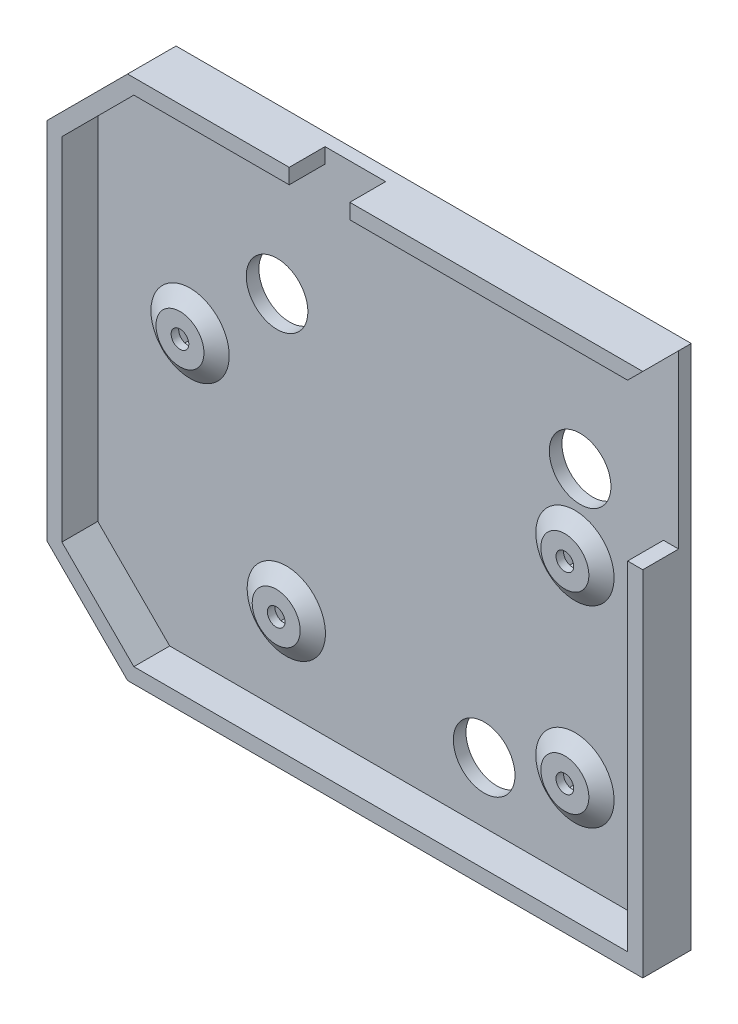
SolidWorks part; units mm, degrees
material "Delrin 2700 NC010, copolymère d'acétal à faible viscosité (SS)"
ref_plane "Plan de face" through (0, 0, 0) normal (0, 0, 1) x (1, 0, 0)
ref_plane "Plan de dessus" through (0, 0, 0) normal (0, 1, 0) x (1, 0, 0)
ref_plane "Plan de droite" through (0, 0, 0) normal (1, 0, 0) x (0, 0, -1)
sketch "Esquisse1" plane through (0, 0, 0) normal (0, 0, 1) x (1, 0, 0)
  line L0 (0, -85) -> (16, -101)
  line L4 (118, 3) -> (118, -101)
  line L5 (16, 3) -> (0, -13)
  line L7 (118, 3) -> (16, 3)
  line L8 (0, -13) -> (0, -85)
  line L9 (16, -101) -> (118, -101)
  dimension "D1" = 104
  dimension "D2" = 118
  dimension "D3" = 16
  dimension "D4" = 16
  dimension "D5" = 16
  dimension "D6" = 16
extrude "Boss.-Extru.1" add sketch "Esquisse1" along normal blind 2.5
sketch "Esquisse2" plane through (0, 0, 2.5) normal (0, 0, 1) x (1, 0, 0)
  line L0 (0, -13) -> (0, -85) construction
  line L1 (3, 0) -> (115, 0) construction
  line L2 (3, 0) -> (3, -98) construction
  line L3 (3, -98) -> (115, -98) construction
  line L4 (115, 0) -> (115, -98) construction
  line L5 (16, -101) -> (118, -101) construction
  line L6 (118, -101) -> (118, 3) construction
  line L7 (118, 3) -> (16, 3) construction
  line L8 (115, -31) -> (118, -31)
  line L9 (3, -83.7574) -> (17.2426, -98)
  line L10 (0, -85) -> (16, -101) construction
  line L11 (3, -14.2426) -> (17.2426, 0)
  line L12 (16, 3) -> (0, -13) construction
  line L14 (3, -14.2426) -> (3, -83.7574)
  line L15 (17.2426, -98) -> (115, -98)
  line L16 (118, 3) -> (118, -101) construction
  line L17 (118, -101) -> (16, -101)
  line L18 (16, -101) -> (0, -85)
  line L19 (0, -85) -> (0, -13)
  line L20 (0, -13) -> (16, 3)
  line L22 (115, 0) -> (118, 3)
  line L23 (115, -98) -> (115, -31)
  line L24 (118, -31) -> (118, -101)
  line L25 (48, 0) -> (48, 3)
  line L26 (60, 0) -> (60, 3)
  line L27 (17.2426, 0) -> (48, 0)
  line L28 (48, 3) -> (16, 3)
  line L29 (60, 3) -> (118, 3)
  line L30 (115, 0) -> (60, 0)
  point P33 (48, 0)
  point P34 (60, 0)
  dimension "D1" = 3
  dimension "D2" = 3
  dimension "D3" = 3
  dimension "D4" = 3
  dimension "D5" = 3
  dimension "D6" = 3
  dimension "D7" = 70
  dimension "D8" = 45
  dimension "D9" = 12
extrude "Boss.-Extru.2" add sketch "Esquisse2" along normal blind 7.1
sketch "Esquisse3" plane through (0, 0, 2.5) normal (0, 0, 1) x (1, 0, 0)
  line L0 (115, -31) -> (115, -98) construction
  line L2 (3, -83.7574) -> (3, -14.2426) construction
  line L3 (115, -31) -> (115, -98) construction
  line L4 (115, -98) -> (17.2426, -98) construction
  line L5 (60, 3) -> (48, 3) construction
  circle A0 centre (98.5, -27) radius 6.1
  circle A1 centre (38.5, -27) radius 6.1
  circle A2 centre (79.5, -86) radius 6.1
  dimension "D1" = 16.5
  dimension "D2" = 30
  dimension "D3" = 30
  dimension "D4" = 35.5
  dimension "D5" = 35.5
  dimension "D6" = 12
extrude "Enlèv. mat.-Extru.1" cut sketch "Esquisse3" against normal blind 10
sketch "Esquisse5" plane through (0, 0, 2.5) normal (0, 0, 1) x (1, 0, 0)
  line L0 (115, -98) -> (17.2426, -98) construction
  line L1 (115, -31) -> (115, -98) construction
  point P0 (21.275, -42.37)
  point P1 (97.475, -42.37)
  point P2 (97.475, -80.47)
  point P3 (40.325, -80.47)
  dimension "D1" = 38.1
  dimension "D2" = 17.53
  dimension "D3" = 17.525
  dimension "D4" = 76.2
  dimension "D5" = 57.15
ref_axis "Axe5" through (21.275, -42.37, 2.5) along (0, 0, 1)
ref_axis "Axe6" through (97.475, -42.37, 2.5) along (0, 0, 1)
ref_axis "Axe7" through (40.325, -80.47, 2.5) along (0, 0, 1)
ref_axis "Axe8" through (97.475, -80.47, 2.5) along (0, 0, 1)
sketch3d "Esquisse3D5"
  line L0 (21.275, -42.37, 2.5) -> (97.475, -42.37, 2.5) construction
  line L1 (40.325, -80.47, 2.5) -> (97.475, -80.47, 2.5) construction
ref_plane "Plan4" through (97.475, -42.37, 2.5) normal (1, 0, 0) x (0, 0, -1)
sketch "Esquisse8" plane through (97.475, -42.37, 2.5) normal (1, 0, 0) x (0, 0, -1)
  line L0 (0, 1.75) -> (0, 7.75)
  line L1 (0, 7.75) -> (-2, 4.75)
  line L2 (-2, 4.75) -> (-2, 1.75)
  line L3 (-2, 1.75) -> (0, 1.75)
  line L5 (0, 0) -> (-50.5083, 0) construction
  point P0 (0, 1.75)
  dimension "D1" = 6
  dimension "D2" = 3
  dimension "D3" = 2
  dimension "D4" = 1.75
revolve "Révolution3" add sketch "Esquisse8" angle 360 about axis through (97.475, -42.37, 2.5) along (0, 0, 1)
ref_plane "Plan5" through (40.325, -80.47, 2.5) normal (1, 0, 0) x (0, 0, -1)
sketch "Esquisse9" plane through (40.325, -80.47, 2.5) normal (1, 0, 0) x (0, 0, -1)
  line L0 (0, 1.75) -> (0, 7.75)
  line L1 (0, 7.75) -> (-2, 4.75)
  line L2 (-2, 4.75) -> (-2, 1.75)
  line L3 (-2, 1.75) -> (0, 1.75)
  point P0 (0, 1.75)
  dimension "D1" = 2
  dimension "D2" = 6
  dimension "D3" = 3
  dimension "D4" = 1.75
revolve "Révolution4" add sketch "Esquisse9" angle 360 about axis through (40.325, -80.47, 2.5) along (0, 0, 1)
ref_plane "Plan6" through (97.475, -80.47, 2.5) normal (1, 0, 0) x (0, 0, -1)
sketch "Esquisse10" plane through (97.475, -80.47, 2.5) normal (1, 0, 0) x (0, 0, -1)
  line L0 (0, 1.75) -> (0, 7.75)
  line L1 (0, 7.75) -> (-2, 4.75)
  line L2 (-2, 4.75) -> (-2, 1.75)
  line L3 (-2, 1.75) -> (0, 1.75)
  point P0 (0, 1.75)
  dimension "D1" = 6
  dimension "D2" = 2
  dimension "D3" = 3
  dimension "D4" = 1.75
revolve "Révolution5" add sketch "Esquisse10" angle 360 about axis through (97.475, -80.47, 2.5) along (0, 0, 1)
hole_wizard "Dégagement M32" positions "Esquisse15" profile "Esquisse16" hole size "M3" standard "Ansi Metric" end condition up to next
sketch "Esquisse15" plane through (0, 0, 2.5) normal (0, 0, 1) x (1, 0, 0)
  point P0 (21.275, -42.37)
  point P3 (40.325, -80.47)
  point P6 (97.475, -42.37)
  point P9 (97.475, -80.47)
sketch "Esquisse16" plane through (21.275, -42.37, 2.5) normal (1, 0, 0) x (0, -1, 0)
  line L0 (0, 0) -> (0, 2.5)
  line L1 (0, 2.5) -> (1.8, 2.5)
  line L2 (1.8, 2.5) -> (1.8, 0)
  line L5 (1.8, 0) -> (0, 0)
  line L11 (0, -6.35) -> (0, 107.95) construction
  dimension "Diamètre du perçage jusqu'au prochain" = 3.6
  dimension "Profondeur du perçage jusqu'au prochain" = 2.5
ref_plane "Plan7" through (21.275, -42.37, 2.5) normal (1, 0, 0) x (0, 0, -1)
sketch "Esquisse17" plane through (21.275, -42.37, 2.5) normal (1, 0, 0) x (0, 0, -1)
  line L1 (0, 1.75) -> (0, 7.75)
  line L2 (0, 7.75) -> (-2, 4.75)
  line L3 (-2, 4.75) -> (-2, 1.75)
  line L4 (-2, 1.75) -> (0, 1.75)
  line L5 (0, 0) -> (-50.5083, 0) construction
  dimension "D1" = 1.75
  dimension "D2" = 6
  dimension "D3" = 3
  dimension "D4" = 2
revolve "Révolution6" add sketch "Esquisse17" angle 360 about axis through (21.275, -42.37, 2.5) along (0, 0, 1)
ref_point "Point1"
ref_point "Point2"
ref_point "Point3"
ref_point "Point4"
sketch "Esquisse18" plane through (0, 0, 0) normal (0, 0, -1) x (-1, 0, 0)
  line L1 (-95.9162, -77.77) -> (-99.0338, -77.77)
  line L2 (-99.0338, -77.77) -> (-100.5927, -80.47)
  line L3 (-100.5927, -80.47) -> (-99.0338, -83.17)
  line L4 (-99.0338, -83.17) -> (-95.9162, -83.17)
  line L5 (-95.9162, -83.17) -> (-94.3573, -80.47)
  line L6 (-94.3573, -80.47) -> (-95.9162, -77.77)
  line L7 (-95.9162, -39.67) -> (-99.0338, -39.67)
  line L8 (-99.0338, -39.67) -> (-100.5927, -42.37)
  line L9 (-100.5927, -42.37) -> (-99.0338, -45.07)
  line L10 (-99.0338, -45.07) -> (-95.9162, -45.07)
  line L11 (-95.9162, -45.07) -> (-94.3573, -42.37)
  line L12 (-94.3573, -42.37) -> (-95.9162, -39.67)
  line L13 (-18.1573, -42.37) -> (-19.7162, -39.67)
  line L14 (-19.7162, -39.67) -> (-22.8338, -39.67)
  line L15 (-22.8338, -39.67) -> (-24.3927, -42.37)
  line L16 (-24.3927, -42.37) -> (-22.8338, -45.07)
  line L17 (-22.8338, -45.07) -> (-19.7162, -45.07)
  line L18 (-19.7162, -45.07) -> (-18.1573, -42.37)
  line L19 (-37.2073, -80.47) -> (-38.7662, -77.77)
  line L20 (-38.7662, -77.77) -> (-41.8838, -77.77)
  line L21 (-41.8838, -77.77) -> (-43.4427, -80.47)
  line L22 (-43.4427, -80.47) -> (-41.8838, -83.17)
  line L23 (-41.8838, -83.17) -> (-38.7662, -83.17)
  line L24 (-38.7662, -83.17) -> (-37.2073, -80.47)
  line L26 (-16, -101) -> (-118, -101) construction
  circle A0 centre (-97.475, -80.47) radius 2.7 construction
  circle A1 centre (-97.475, -42.37) radius 2.7 construction
  circle A2 centre (-21.275, -42.37) radius 2.7 construction
  circle A3 centre (-40.325, -80.47) radius 2.7 construction
  point P28 (-94.3611, -42.1924)
  dimension "D1" = 5.4
  dimension "D2" = 5.4
  dimension "D3" = 5.4
  dimension "D4" = 5.4
extrude "Enlèv. mat.-Extru.2" cut sketch "Esquisse18" against normal blind 3
